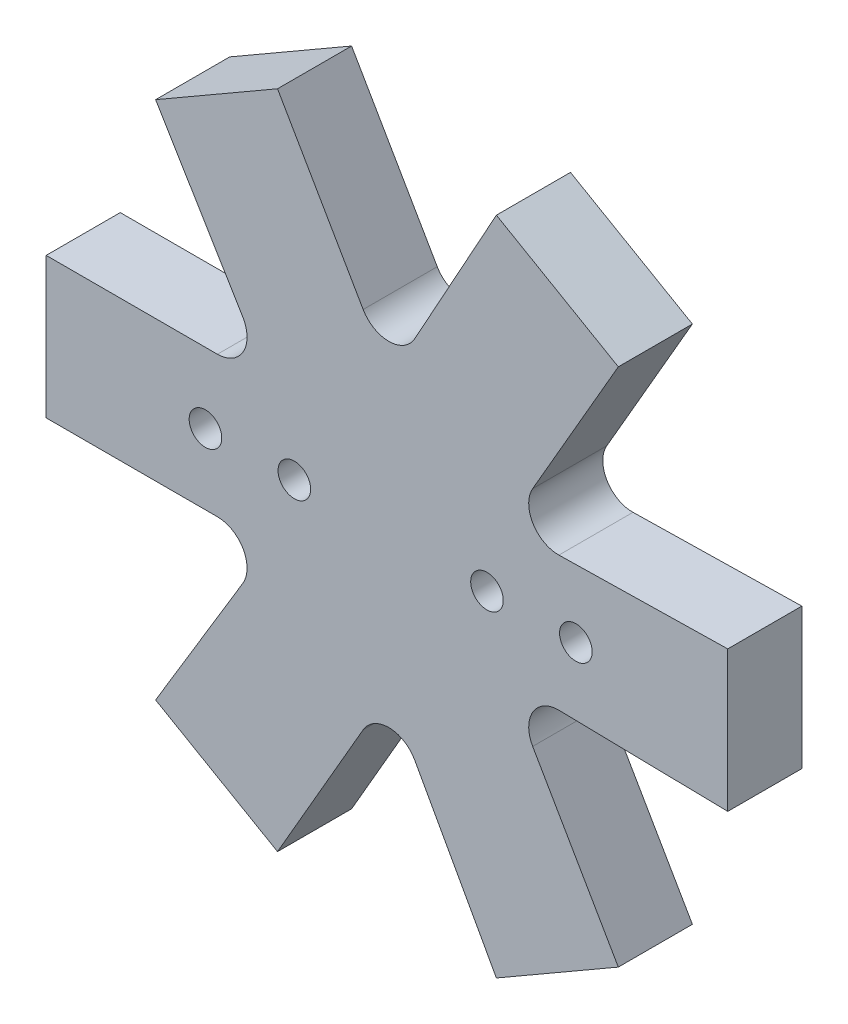
SolidWorks part; units mm, degrees
ref_plane "Front Plane" through (0, 0, 0) normal (0, 0, 1) x (1, 0, 0)
ref_plane "Top Plane" through (0, 0, 0) normal (0, 1, 0) x (1, 0, 0)
ref_plane "Right Plane" through (0, 0, 0) normal (1, 0, 0) x (0, 0, -1)
sketch "Sketch1" plane through (0, 0, 0) normal (0, 0, 1) x (1, 0, 0)
  line L4 (-23.25, 4.75) -> (-23.25, -4.75)
  line L5 (-7.6364, 22.2936) -> (-15.8636, 17.5436)
  line L8 (15.3636, 17.5436) -> (7.1364, 22.2936)
  line L11 (22.75, -4.75) -> (22.75, 4.75)
  line L14 (7.1364, -22.2936) -> (15.3636, -17.5436)
  line L17 (-15.8636, -17.5436) -> (-7.6364, -22.2936)
  line L18 (11.3543, 4.5339) -> (22.75, 4.75)
  line L19 (9.5843, 7.5335) -> (15.3636, 17.5436)
  line L20 (9.5843, -7.5335) -> (15.3636, -17.5436)
  line L21 (11.3543, -4.5339) -> (22.75, -4.75)
  line L22 (-1.8571, -12.2835) -> (-7.6364, -22.2936)
  line L23 (1.6257, -12.3165) -> (7.1364, -22.2936)
  line L24 (-11.6913, -4.75) -> (-23.25, -4.75)
  line L25 (-9.9786, -7.7827) -> (-15.8636, -17.5436)
  line L26 (-9.9786, 7.7827) -> (-15.8636, 17.5436)
  line L27 (-11.6913, 4.75) -> (-23.25, 4.75)
  line L28 (1.6257, 12.3165) -> (7.1364, 22.2936)
  line L29 (-1.8571, 12.2835) -> (-7.6364, 22.2936)
  arc A0 (11.3543, -4.5339) -> (9.5843, -7.5335) centre (11.3163, -6.5335) ccw
  arc A1 (1.6257, -12.3165) -> (-1.8571, -12.2835) centre (-0.125, -13.2835) ccw
  arc A2 (-9.9786, -7.7827) -> (-11.6913, -4.75) centre (-11.6913, -6.75) ccw
  arc A3 (-11.6913, 4.75) -> (-9.9786, 7.7827) centre (-11.6913, 6.75) ccw
  arc A4 (-1.8571, 12.2835) -> (1.6257, 12.3165) centre (-0.125, 13.2835) ccw
  arc A5 (9.5843, 7.5335) -> (11.3543, 4.5339) centre (11.3163, 6.5335) ccw
  point P2 (0, 0)
  point P6 (0, 0)
  point P7 (0, 0)
  point P11 (0, 0)
  point P12 (0, 0)
  dimension "D1" = 2
  dimension "D2" = 9.5
  dimension "D3" = 6
  dimension "D4" = 46
extrude "Boss-Extrude2" add sketch "Sketch1" along normal blind 5
sketch "Sketch2" plane through (0, 0, 0) normal (0, 0, -1) x (-1, 0, 0)
  line L0 (0, 0) -> (0, 14.25) construction
  line L1 (0, 0) -> (14, 0) construction
  line L2 (0.7806, 4.1777) -> (12.6173, 1.966)
  line L3 (0.7806, -4.1777) -> (12.6173, -1.966)
  line L4 (-0.7806, -4.1777) -> (-12.6173, -1.966)
  line L5 (-0.7806, 4.1777) -> (-12.6173, 1.966)
  circle A0 centre (0, 0) radius 14.25 construction
  arc A1 (0.7806, 4.1777) -> (-0.7806, 4.1777) centre (0, 0) ccw
  arc A2 (12.6173, -1.966) -> (12.6173, 1.966) centre (12.25, 0) ccw
  arc A3 (0.7806, -4.1777) -> (-0.7806, -4.1777) centre (0, 0) cw
  arc A4 (-12.6173, -1.966) -> (-12.6173, 1.966) centre (-12.25, 0) cw
  dimension "D1" = 28.5
  dimension "D2" = 8.5
  dimension "D3" = 4
extrude "Cut-Extrude1" cut sketch "Sketch2" against normal blind 2
sketch "Sketch3" plane through (0, 0, 2) normal (0, 0, -1) x (-1, 0, 0)
  line L0 (0, 0) -> (-14.25, 0) construction
  line L1 (0, 0) -> (0, 4.25) construction
  arc A0 (-12.6173, 1.966) -> (-12.6173, -1.966) centre (-12.25, 0) ccw construction
  arc A1 (0.7806, 4.1777) -> (-0.7806, 4.1777) centre (0, 0) ccw construction
  circle A2 centre (-6.5, 0) radius 1.1
  circle A3 centre (-12.5, 0) radius 1.1
  circle A4 centre (6.5, 0) radius 1.1
  circle A5 centre (12.5, 0) radius 1.1
  dimension "D2" = 2.2
  dimension "D3" = 2.2
  dimension "D1" = 6.5
  dimension "D4" = 12.5
extrude "Cut-Extrude2" cut sketch "Sketch3" against normal through all
